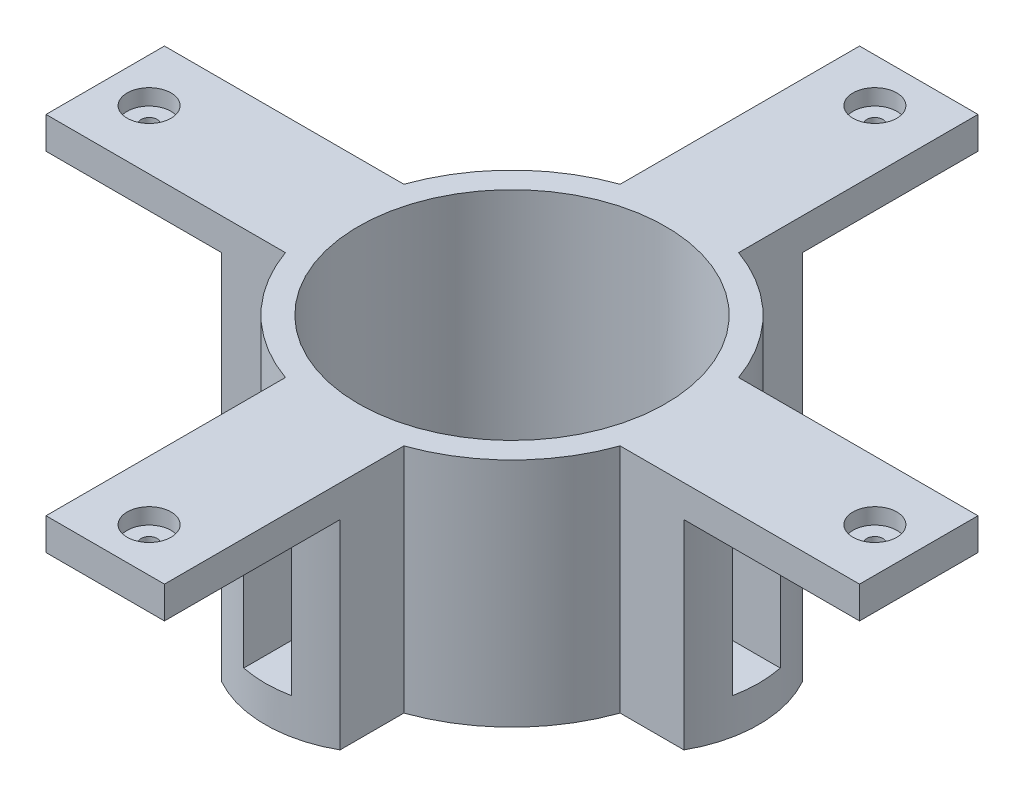
SolidWorks part; units mm, degrees
ref_plane "Front Plane" through (0, 0, 0) normal (0, 0, 1) x (1, 0, 0)
ref_plane "Top Plane" through (0, 0, 0) normal (0, 1, 0) x (1, 0, 0)
ref_plane "Right Plane" through (0, 0, 0) normal (1, 0, 0) x (0, 0, -1)
sketch "Sketch1" plane through (0, 0, 0) normal (0, 1, 0) x (1, 0, 0)
  circle A0 centre (0, 0) radius 44.5
  circle A1 centre (0, 0) radius 38.5
  dimension "D1" = 89
  dimension "D2" = 6
extrude "Boss-Extrude1" add sketch "Sketch1" along normal blind 8
sketch "Sketch2" plane through (0, 0, 0) normal (0, 1, 0) x (1, 0, 0)
  line L0 (22.25, 0) -> (102.1285, 0) construction
  line L1 (41.9511, 14.8444) -> (101.9511, 14.8444)
  line L2 (41.9511, -14.8444) -> (101.9511, -14.8444)
  line L3 (101.9511, 14.8444) -> (101.9511, -14.8444)
  circle A0 centre (0, 0) radius 44.5 construction
  arc A3 (41.9511, 14.8444) -> (41.9511, -14.8444) centre (0, 0) cw
  circle A7 centre (90.9511, 0) radius 2
  dimension "D1" = 4
  dimension "D2" = 11
  dimension "D3" = 60
extrude "Boss-Extrude2" add sketch "Sketch2" along normal blind 8
pattern_circular "CirPattern3" count 4 every 90 about axis through (0, 8, 0) along (0, -1, 0) of "Boss-Extrude2" reverse direction yes
sketch "Sketch5" plane through (0, 0, 0) normal (0, 1, 0) x (1, 0, 0)
  circle A0 centre (0, 0) radius 44.5
  circle A1 centre (0, 0) radius 38.5
extrude "Boss-Extrude3" add sketch "Sketch5" against normal blind 50
sketch "Sketch7" plane through (0, 0, 0) normal (0, 1, 0) x (1, 0, 0)
  line L0 (41.9511, 14.8444) -> (57.9511, 14.8444)
  line L1 (101.9511, 14.8444) -> (41.9511, 14.8444) construction
  line L2 (41.9511, -14.8444) -> (57.9511, -14.8444)
  line L3 (41.9511, -14.8444) -> (101.9511, -14.8444) construction
  arc A1 (41.9511, 14.8444) -> (41.9511, -14.8444) centre (0, 0) cw
  arc A2 (57.9511, 14.8444) -> (57.9511, -14.8444) centre (31.5625, 0) cw
  circle A3 centre (51.9, 0) radius 2
  point P15 (0, 0)
  dimension "D1" = 4
  dimension "D2" = 51.9
  dimension "D3" = 16
extrude "Boss-Extrude4" add sketch "Sketch7" against normal blind 50
pattern_circular "CirPattern4" count 4 every 90 about axis through (0, 8, 0) along (0, -1, 0) of "Boss-Extrude4"
sketch "Sketch8" plane through (0, 0, 0) normal (0, -1, 0) x (1, 0, 0)
  line L0 (61.8398, 0) -> (28.6461, 0) construction
  line L1 (61.2393, -6) -> (45.9, -6)
  line L2 (45.9, -6) -> (45.9, 6)
  line L3 (61.2393, 6) -> (45.9, 6)
  arc A0 (57.9511, -14.8444) -> (57.9511, 14.8444) centre (31.5625, 0) ccw construction
  arc A1 (57.9511, -14.8444) -> (57.9511, 14.8444) centre (31.5625, 0) ccw construction
  circle A2 centre (51.9, 0) radius 2 construction
  arc A3 (61.2393, 6) -> (61.2393, -6) centre (31.5625, 0) cw
  point P15 (45.9, 0)
  dimension "D1" = 6
  dimension "D2" = 6
extrude "Cut-Extrude2" cut sketch "Sketch8" along normal blind 41
pattern_circular "CirPattern5" count 4 every 90 about axis through (0, 8, 0) along (0, -1, 0) of "Cut-Extrude2"
sketch "Sketch9" plane through (0, 8, 0) normal (0, 1, 0) x (1, 0, 0)
  circle A0 centre (90.9511, 0) radius 5.5
  circle A1 centre (90.9511, 0) radius 2 construction
  dimension "D1" = 3.5
extrude "Cut-Extrude3" cut sketch "Sketch9" against normal blind 4
pattern_circular "CirPattern6" count 4 every 90 about axis through (0, 8, 0) along (0, -1, 0) of "Cut-Extrude3"
